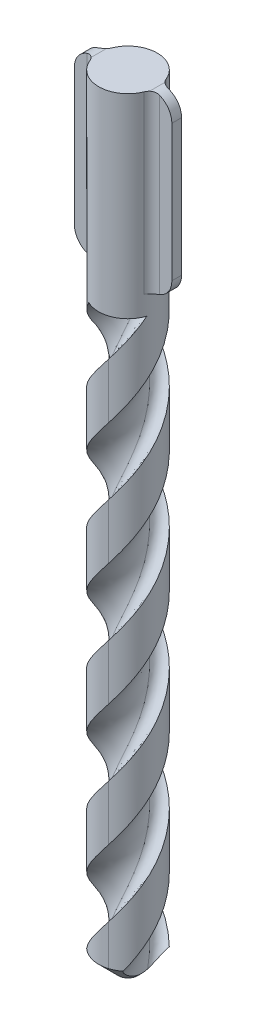
SolidWorks part; units mm, degrees
material "1023 Carbon Steel Sheet (SS)"
ref_plane "Front Plane" through (0, 0, 0) normal (0, 0, 1) x (1, 0, 0)
ref_plane "Top Plane" through (0, 0, 0) normal (0, 1, 0) x (1, 0, 0)
ref_plane "Right Plane" through (0, 0, 0) normal (1, 0, 0) x (0, 0, -1)
sketch "Sketch1" plane through (0, 0, 0) normal (0, 1, 0) x (1, 0, 0)
  circle A0 centre (0, 0) radius 3
  dimension "D1" = 6
extrude "Boss-Extrude1" add sketch "Sketch1" against normal blind 80
sketch "Sketch2" plane through (0, 0, 0) normal (0, 1, 0) x (1, 0, 0)
  line L1 (5, -0.5) -> (-5, -0.5)
  line L2 (5, -0.5) -> (5, 0.5)
  line L3 (5, 0.5) -> (-5, 0.5)
  line L4 (-5, -0.5) -> (-5, 0.5)
  line L5 (5, -0.5) -> (-5, 0.5) construction
  line L6 (5, 0.5) -> (-5, -0.5) construction
  point P0 (0, 0)
  dimension "D1" = 10
  dimension "D2" = 1
extrude "Boss-Extrude2" add sketch "Sketch2" against normal blind 18
fillet "Fillet1" radius 1 4 edges at (-2.958, -9, -0.5) (2.958, -9, -0.5) (2.958, -9, 0.5) (-2.958, -9, 0.5)
sketch "Sketch3" plane through (0, -80, 0) normal (0, 1, 0) x (1, 0, 0)
  line L0 (-1.5479, -0.3057) -> (-0.5, 2.958)
  line L1 (0, -3.3) -> (0, 3.3) construction
  line L2 (-3.3, 0.6) -> (-2.4, 1.8)
  circle A0 centre (0, 0) radius 2.5 construction
  arc A1 (-3.3, 0.6) -> (-1.5479, -0.3057) centre (-2.5, 0) ccw
  arc A2 (-0.5, 2.958) -> (-2.4, 1.8) centre (0, 0) ccw
  circle A3 centre (0, 0) radius 1.3803 construction
  dimension "D1" = 5
  dimension "D2" = 2
  dimension "D3" = 3
  dimension "D4" = 0.5
sketch "Sketch4" plane through (0, -80, 0) normal (0, -1, 0) x (1, 0, 0)
  circle A0 centre (0, 0) radius 3
curve "Helix/Spiral1" pitch 25 height 60 radius 3 centre (0, -80, 0) axis (0, 1, 0) start towards (0, 0, -1)
sweep "Cut-Sweep1" cut profiles "Sketch3" path "Helix/Spiral1" align with end faces yes
pattern_circular "CirPattern1" count 2 every 180 about axis through (0, -80, 0) along (0, 1, 0) of "Cut-Sweep1" reverse direction yes
ref_axis "Axis1" through (0, -80.0053, 0) along (0, 1, 0)
fillet "Fillet2" radius 2 4 edges at (-5, 0, 0) (5, 0, 0) (5, -18, 0) (-5, -18, 0)
sketch "Sketch6" plane through (0, 0, 0) normal (0, 0, 1) x (1, 0, 0)
  line L0 (-1, -80) -> (-3, -78)
  line L1 (-3, -78) -> (-3, -80)
  line L2 (-3, -80) -> (-1, -80)
  line L3 (-3, -80.2722) -> (-3, -78.4059) construction
  line L4 (0, -80.0053) -> (0, 0) construction
  line L5 (-2.85, -80) -> (0.5, -80) construction
  dimension "D1" = 45
  dimension "D2" = 3
  dimension "D3" = 1
revolve "Cut-Revolve2" cut sketch "Sketch6" angle 360 about axis through (0, -80.0053, 0) along (0, 1, 0)
